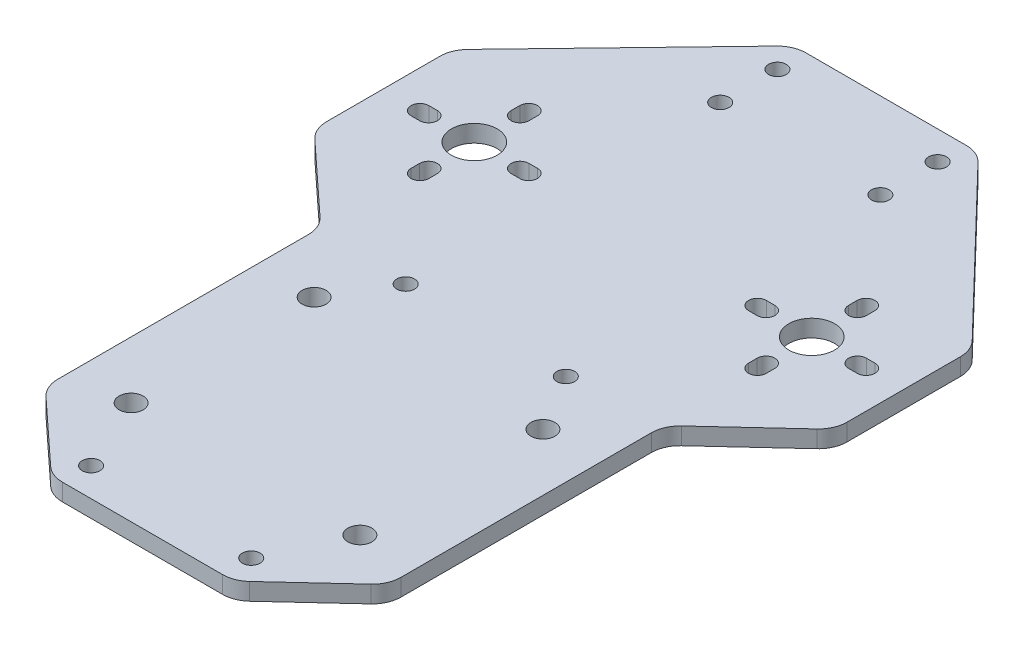
SolidWorks part; units mm, degrees
material "Thornel Mat VMA"
ref_plane "Front Plane" through (0, 0, 0) normal (0, 0, 1) x (1, 0, 0)
ref_plane "Top Plane" through (0, 0, 0) normal (0, 1, 0) x (1, 0, 0)
ref_plane "Right Plane" through (0, 0, 0) normal (1, 0, 0) x (0, 0, -1)
sketch "Sketch1" plane through (0, 0, 0) normal (0, 1, 0) x (1, 0, 0)
  line L0 (0, 0) -> (0, -82.5) construction
  line L1 (29.5, 0) -> (0, 0) construction
  line L2 (37.5, 0) -> (39, 0) construction
  line L3 (37.5, 1.55) -> (39, 1.55)
  line L4 (37.5, -1.55) -> (39, -1.55)
  line L5 (29.5, -8) -> (29.5, -9.5) construction
  line L6 (31.05, -8) -> (31.05, -9.5)
  line L7 (27.95, -8) -> (27.95, -9.5)
  line L8 (21.5, 0) -> (20, 0) construction
  line L9 (21.5, -1.55) -> (20, -1.55)
  line L10 (21.5, 1.55) -> (20, 1.55)
  line L11 (29.5, 8) -> (29.5, 9.5) construction
  line L12 (27.95, 8) -> (27.95, 9.5)
  line L13 (31.05, 8) -> (31.05, 9.5)
  line L14 (-37.5, 0) -> (-39, 0) construction
  line L19 (14, -27.5) -> (-14, -27.5) construction
  line L22 (14, -27.5) -> (14, 27.5) construction
  line L25 (14, 27.5) -> (-14, 27.5) construction
  line L28 (-14, -27.5) -> (-14, 27.5) construction
  line L38 (14, -27.5) -> (-14, 27.5) construction
  line L41 (45.5, 42.5) -> (-45.5, 42.5)
  line L44 (45.5, 42.5) -> (45.5, -87.5)
  line L47 (45.5, -87.5) -> (-45.5, -87.5)
  line L50 (-45.5, 42.5) -> (-45.5, -87.5)
  line L59 (-959, -57) -> (49041, -57) construction
  line L65 (14, 27.5) -> (-14, -27.5) construction
  line L66 (-14, 37.5) -> (14, 37.5) construction
  line L67 (-14, 37.5) -> (-14, 27.5) construction
  line L69 (14, 37.5) -> (14, 27.5) construction
  line L74 (-14, -27.5) -> (-14, -82.5) construction
  line L75 (-14, -82.5) -> (14, -82.5) construction
  line L76 (14, -82.5) -> (14, -27.5) construction
  line L77 (-20, -37.5) -> (20, -37.5) construction
  line L78 (-20, -37.5) -> (-20, -69.5) construction
  line L79 (-20, -69.5) -> (20, -69.5) construction
  line L80 (20, -37.5) -> (20, -69.5) construction
  line L81 (-20, -37.5) -> (20, -69.5) construction
  line L82 (-20, -69.5) -> (20, -37.5) construction
  line L83 (-37.5, 1.55) -> (-39, 1.55)
  line L84 (-37.5, -1.55) -> (-39, -1.55)
  line L85 (-29.5, 8) -> (-29.5, 9.5) construction
  line L86 (-27.95, 8) -> (-27.95, 9.5)
  line L87 (-31.05, 8) -> (-31.05, 9.5)
  line L88 (-21.5, 0) -> (-20, 0) construction
  line L89 (-21.5, -1.55) -> (-20, -1.55)
  line L90 (-21.5, 1.55) -> (-20, 1.55)
  line L91 (-29.5, -8) -> (-29.5, -9.5) construction
  line L92 (-31.05, -8) -> (-31.05, -9.5)
  line L93 (-27.95, -8) -> (-27.95, -9.5)
  line L94 (0, -82.5) -> (0, -87.5) construction
  circle A0 centre (29.5, 0) radius 4
  arc A1 (37.5, 1.55) -> (37.5, -1.55) centre (37.5, 0) ccw
  arc A2 (39, -1.55) -> (39, 1.55) centre (39, 0) ccw
  arc A3 (31.05, -8) -> (27.95, -8) centre (29.5, -8) ccw
  arc A4 (27.95, -9.5) -> (31.05, -9.5) centre (29.5, -9.5) ccw
  arc A5 (21.5, -1.55) -> (21.5, 1.55) centre (21.5, 0) ccw
  arc A6 (20, 1.55) -> (20, -1.55) centre (20, 0) ccw
  arc A7 (27.95, 8) -> (31.05, 8) centre (29.5, 8) ccw
  arc A8 (31.05, 9.5) -> (27.95, 9.5) centre (29.5, 9.5) ccw
  circle A22 centre (14, 27.5) radius 1.55
  circle A23 centre (14, -27.5) radius 1.55
  circle A24 centre (-14, -27.5) radius 1.55
  circle A25 centre (-14, 27.5) radius 1.55
  circle A76 centre (-14, 37.5) radius 1.55
  circle A77 centre (14, 37.5) radius 1.55
  circle A78 centre (20, -69.5) radius 2.1
  circle A79 centre (-20, -69.5) radius 2.1
  circle A91 centre (-14, -82.5) radius 1.55
  circle A92 centre (14, -82.5) radius 1.55
  circle A93 centre (-20, -37.5) radius 2.1
  circle A94 centre (20, -37.5) radius 2.1
  arc A95 (-37.5, 1.55) -> (-37.5, -1.55) centre (-37.5, 0) cw
  arc A96 (-39, -1.55) -> (-39, 1.55) centre (-39, 0) cw
  arc A97 (-27.95, 8) -> (-31.05, 8) centre (-29.5, 8) cw
  arc A98 (-31.05, 9.5) -> (-27.95, 9.5) centre (-29.5, 9.5) cw
  arc A99 (-21.5, -1.55) -> (-21.5, 1.55) centre (-21.5, 0) cw
  arc A100 (-20, 1.55) -> (-20, -1.55) centre (-20, 0) cw
  arc A101 (-31.05, -8) -> (-27.95, -8) centre (-29.5, -8) cw
  arc A102 (-27.95, -9.5) -> (-31.05, -9.5) centre (-29.5, -9.5) cw
  circle A103 centre (-29.5, 0) radius 4
  point P1 (0, -53.5)
  point P8 (38.25, 0)
  point P18 (29.5, -8.75)
  point P25 (20.75, 0)
  point P32 (29.5, 8.75)
  point P37 (29.5, 0)
  point P46 (-38.25, 0)
  point P51 (0, 32.5)
  point P54 (-29.5, 8.75)
  point P61 (-20.75, 0)
  point P68 (-29.5, -8.75)
  dimension "D1" = 8
  dimension "D2" = 1.55
  dimension "D4" = 8
  dimension "D5" = 4
  dimension "D6" = 5
  dimension "D7" = 5
  dimension "D8" = 40
  dimension "D9" = 32
  dimension "D10" = 3.1
  dimension "D11" = 10
  dimension "D12" = 55
  dimension "D13" = 16
  dimension "D15" = 10
  dimension "D19" = 28
  dimension "D20" = 29.5
  dimension "D27" = 4.2
  dimension "D3" = 1.5
  dimension "D14" = 55
extrude "凸台-拉伸1" add sketch "Sketch1" along normal blind 3 contours L41 L50 L47 L44 A79 A78 A23 A22 A0 A2 L4 A1 L3 A4 L7 A3 L6 A6 L10 A5 L9 A8 L13 A7 L12 region at (0, 0, 22.7969)
sketch "草图8" plane through (0, 0, 0) normal (0, 1, 0) x (1, 0, 0)
  line L3 (45.5, 42.5) -> (45.5, 12)
  line L13 (0, 42.5) -> (0, -87.5) construction
  line L15 (45.5, 42.5) -> (-45.5, 42.5) construction
  line L16 (45.5, -87.5) -> (-45.5, -87.5) construction
  line L17 (16.1264, 42.5) -> (45.5, 42.5)
  line L19 (16.1264, 42.5) -> (45.5, 12)
  line L20 (45.5, 42.5) -> (45.5, -87.5) construction
  line L21 (45.5, 12) -> (45.5, -12) construction
  line L22 (45.5, -12) -> (30, -26.3511)
  line L23 (30, -26.3511) -> (30, -74.5)
  line L24 (30, -74.5) -> (15.9593, -87.5)
  line L25 (45.5, -12) -> (45.5, -87.5)
  line L27 (45.5, -87.5) -> (15.9593, -87.5)
  line L28 (45.5, 0) -> (29.5, 0) construction
  line L29 (-45.5, -87.5) -> (-15.9593, -87.5)
  line L30 (-30, -74.5) -> (-15.9593, -87.5)
  line L31 (-30, -26.3511) -> (-30, -74.5)
  line L32 (-45.5, -12) -> (-45.5, -87.5)
  line L33 (-45.5, -12) -> (-30, -26.3511)
  line L34 (-16.1264, 42.5) -> (-45.5, 12)
  line L35 (-16.1264, 42.5) -> (-45.5, 42.5)
  line L36 (-45.5, 42.5) -> (-45.5, 12)
  circle A1 centre (14, 37.5) radius 1.55 construction
  circle A2 centre (20, -37.5) radius 2.1 construction
  circle A3 centre (20, -69.5) radius 2.1 construction
  circle A4 centre (14, -82.5) radius 1.55 construction
  dimension "D1" = 5
  dimension "D2" = 10
  dimension "D3" = 5
  dimension "D4" = 5
  dimension "D5" = 12
extrude "切除-拉伸1" cut sketch "草图8" along normal up to next contours L21 | L35 L36 L34 | L33 L32 L29 L30 L31 | L3 L19 L17 | L25 L27 L24 L23 L22 region at (-37.0136, 0, 55.5888) region at (-35.7088, 0, -32.3333)
fillet "圆角1" radius 5 12 edges at (-45.5, 1.5, 12) (-45.5, 1.5, -12) (-16.1264, 1.5, -42.5) (45.5, 1.5, -12) (45.5, 1.5, 12) (30, 1.5, 26.3511) (30, 1.5, 74.5) (15.9593, 1.5, 87.5) (-15.9593, 1.5, 87.5) (-30, 1.5, 74.5) (-30, 1.5, 26.3511) (16.1264, 1.5, -42.5) first distance on face at (-45.5, 1.5, 0) first distance on face at (-30.8132, 1.5, -27.25) first distance on face at (0, 1.5, -42.5) first distance on face at (45.5, 1.5, 0) first distance on face at (37.75, 1.5, 19.1756) first distance on face at (30, 1.5, 50.4256) first distance on face at (22.9796, 1.5, 81) first distance on face at (0, 1.5, 87.5) first distance on face at (-22.9796, 1.5, 81) first distance on face at (-30, 1.5, 50.4256) first distance on face at (-37.75, 1.5, 19.1756) first distance on face at (30.8132, 1.5, -27.25)
